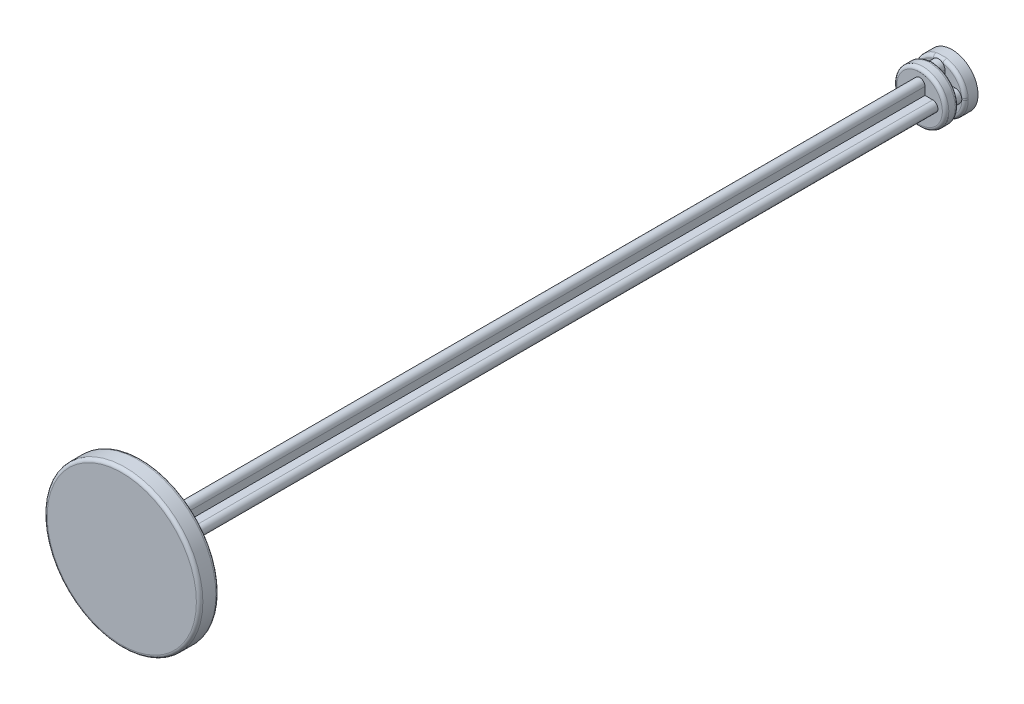
SolidWorks part; units mm, degrees
material "PVC Rigid"
ref_plane "Front Plane" through (0, 0, 0) normal (0, 0, 1) x (1, 0, 0)
ref_plane "Top Plane" through (0, 0, 0) normal (0, 1, 0) x (1, 0, 0)
ref_plane "Right Plane" through (0, 0, 0) normal (1, 0, 0) x (0, 0, -1)
sketch "Sketch3" plane through (0, 0, 0) normal (0, 0, 1) x (1, 0, 0)
  line L0 (-0.3894, 0.3966) -> (-0.3894, 0.9966)
  line L1 (-0.3894, 0.3966) -> (0.4106, 0.3966) construction
  line L2 (-0.3894, 0.3966) -> (-0.3894, -0.4034) construction
  line L3 (-0.3894, -0.4034) -> (0.4106, -0.4034) construction
  line L4 (0.4106, 0.3966) -> (0.4106, -0.4034) construction
  line L5 (-0.3894, 0.3966) -> (0.4106, -0.4034) construction
  line L6 (-0.3894, -0.4034) -> (0.4106, 0.3966) construction
  line L7 (0.4106, 0.3966) -> (0.4106, 0.9966)
  line L8 (0.4106, -0.4034) -> (1.0106, -0.4034)
  line L9 (0.4106, 0.3966) -> (1.0106, 0.3966)
  line L10 (-0.3894, -0.4034) -> (-0.3894, -1.0034)
  line L11 (0.4106, -0.4034) -> (0.4106, -1.0034)
  line L12 (-0.3894, 0.3966) -> (-0.9894, 0.3966)
  line L13 (-0.3894, -0.4034) -> (-0.9894, -0.4034)
  arc A0 (-0.3894, 0.9966) -> (0.4106, 0.9966) centre (0.0106, 0.9966) cw
  arc A1 (1.0106, 0.3966) -> (1.0106, -0.4034) centre (1.0106, -0.0034) cw
  arc A2 (0.4106, -1.0034) -> (-0.3894, -1.0034) centre (0.0106, -1.0034) cw
  arc A3 (-0.9894, -0.4034) -> (-0.9894, 0.3966) centre (-0.9894, -0.0034) cw
  point P25 (0.0106, -0.0034)
  dimension "D1" = 0.8
  dimension "D2" = 0.8
  dimension "D3" = 0.6
  dimension "D4" = 4
extrude "Boss-Extrude1" add sketch "Sketch3" along normal blind 60 contours A3 L13 L10 A2 L11 L8 A1 L9 L7 A0 L0 L12 region at (0.0106, -0.0034, 0)
sketch "Sketch4" plane through (0, 0, 60) normal (0, 0, 1) x (1, 0, 0)
  circle A0 centre (0, 0) radius 6
  dimension "D1" = 12
extrude "Boss-Extrude2" add sketch "Sketch4" along normal blind 1.5
sketch "Sketch5" plane through (0, 0, 0) normal (0, 0, -1) x (-1, 0, 0)
  circle A0 centre (0, 0) radius 2
  dimension "D1" = 4
extrude "Boss-Extrude3" add sketch "Sketch5" along normal blind 1
sketch "Sketch6" plane through (0, 0, -1) normal (0, 0, -1) x (-1, 0, 0)
  line L0 (-0.4513, 0.5617) -> (-0.4513, 1.3617)
  line L1 (-0.4513, 0.5617) -> (0.5487, 0.5617) construction
  line L2 (-0.4513, 0.5617) -> (-0.4513, -0.2383) construction
  line L3 (-0.4513, -0.2383) -> (0.5487, -0.2383) construction
  line L4 (0.5487, 0.5617) -> (0.5487, -0.2383) construction
  line L5 (0.5487, 0.5617) -> (0.5487, 1.3617)
  line L6 (0.5487, -0.4383) -> (1.3487, -0.4383)
  line L7 (0.5487, 0.5617) -> (1.3487, 0.5617)
  line L8 (-0.4513, -0.4383) -> (-0.4513, -1.2383)
  line L9 (0.5487, -0.4383) -> (0.5487, -1.2383)
  line L10 (-0.4513, 0.5617) -> (-1.2513, 0.5617)
  line L11 (-0.4513, -0.4383) -> (-1.2513, -0.4383)
  arc A0 (-0.4513, 1.3617) -> (0.5487, 1.3617) centre (0.0487, 1.3617) cw
  arc A1 (1.3487, 0.5617) -> (1.3487, -0.4383) centre (1.3487, 0.0617) cw
  arc A2 (0.5487, -1.2383) -> (-0.4513, -1.2383) centre (0.0487, -1.2383) cw
  arc A3 (-1.2513, -0.4383) -> (-1.2513, 0.5617) centre (-1.2513, 0.0617) cw
  point P25 (0.0487, 0.0617)
  dimension "D1" = 0.8
  dimension "D2" = 1
  dimension "D3" = 0.8
  dimension "D4" = 4
extrude "Boss-Extrude4" add sketch "Sketch6" along normal blind 0.5
sketch "Sketch9" plane through (0, 0, -1.5) normal (0, 0, -1) x (-1, 0, 0)
  circle A0 centre (0, 0) radius 2
  dimension "D1" = 4
extrude "Boss-Extrude5" add sketch "Sketch9" along normal blind 1
dome "Dome1" faces to dome 1 distance 0.5 reverse direction no elliptical dome no face at (-2, 0, -2.5) parameters "D1"=0.5
fillet "Fillet1" radius 0.25 5 edges at (-2, 0, -1.5) (6, 0, 61.5) (6, 0, 60) (-2, 0, 0) (-2, 0, -1)
